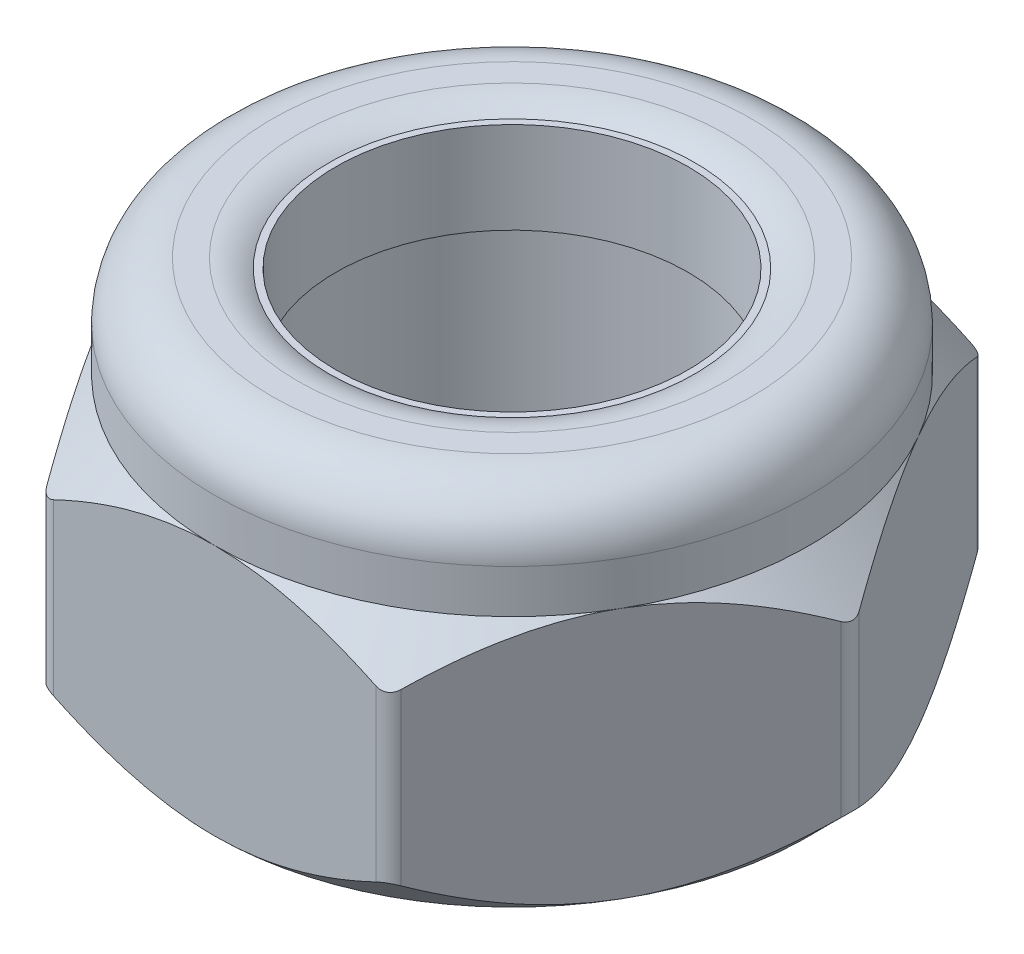
SolidWorks part; units mm, degrees
material "铸造碳钢"
ref_plane "Front" through (0, 0, 0) normal (0, 0, 1) x (1, 0, 0)
ref_plane "Top" through (0, 0, 0) normal (0, 1, 0) x (1, 0, 0)
ref_plane "Right" through (0, 0, 0) normal (1, 0, 0) x (0, 0, -1)
other "配置表"
sketch "草图1" plane through (0, 0, 0) normal (0, 1, 0) x (1, 0, 0)
  line L1 (7.5056, 0) -> (3.7528, 6.5)
  line L2 (3.7528, 6.5) -> (-3.7528, 6.5)
  line L3 (-3.7528, 6.5) -> (-7.5056, 0)
  line L4 (-7.5056, 0) -> (-3.7528, -6.5)
  line L5 (-3.7528, -6.5) -> (3.7528, -6.5)
  line L6 (3.7528, -6.5) -> (7.5056, 0)
  circle A0 centre (0, 0) radius 6.5 construction
  dimension "六角对边长" = 13
extrude "凸台-拉伸1" add sketch "草图1" along normal mid plane 5.5
sketch "草图3" plane through (0, 2.75, 0) normal (0, 1, 0) x (1, 0, 0)
  circle A0 centre (0, 0) radius 6.5
  dimension "圆形外直径" = 13
extrude "凸台-拉伸2" add sketch "草图3" along normal blind 2.2
sketch "草图4" plane through (0, 4.95, 0) normal (0, 1, 0) x (1, 0, 0)
  circle A0 centre (0, 0) radius 4
  dimension "螺母内径" = 8
extrude "切除-拉伸1" cut sketch "草图4" against normal through all
sketch "草图5" plane through (0, 4.95, 0) normal (0, 1, 0) x (1, 0, 0)
  circle A0 centre (0, 0) radius 4
  circle A1 centre (0, 0) radius 3.85
  dimension "橡胶内径" = 7.7
  dimension "橡皮圈外直径" = 8
extrude "凸台-拉伸3" add sketch "草图5" against normal up to surface (2.2 mm away) from offset 0.2 up to face at (-6.5449, 2.75, 0) offset against normal yes
fillet "圆角1" radius 1.25 2 edges at (0, 4.95, 4) (0, 4.95, 6.5)
sketch "草图6" plane through (0, 0, 0) normal (0, 0, 1) x (1, 0, 0)
  line L0 (0, -1000) -> (0, 49000) construction
  line L1 (-1000, 0) -> (49000, 0) construction
  line L2 (-7.5056, 2.75) -> (-7.5056, 1.7444)
  line L3 (-7.5056, 1.7444) -> (-6.5, 2.75)
  line L4 (-6.5, 2.75) -> (-7.5056, 2.75)
  line L5 (0, 2.75) -> (-5.6292, 2.75) construction
  line L6 (-7.5056, 2.75) -> (-7.5056, -2.75) construction
  line L7 (-6.5, -998.4247) -> (-6.5, 49001.5753) construction
  line L8 (-6.5, 3.7) -> (-6.5, 2.75) construction
  line L9 (-7.5056, -2.75) -> (-7.5056, -1.7444)
  line L10 (-7.5056, -1.7444) -> (-6.5, -2.75)
  line L11 (-6.5, -2.75) -> (-7.5056, -2.75)
  dimension "D1" = 45
revolve "切除-旋转1" cut sketch "草图6" angle 360 about L0
fillet "圆角3" radius 0.4 6 edges at (-7.5056, 0, 0) (-3.7528, 0, -6.5) (3.7528, 0, -6.5) (7.5056, 0, 0) (3.7528, 0, 6.5) (-3.7528, 0, 6.5)
move or copy body "实体-移动/复制1" [suppressed] bodies to move or copy 105
move or copy body "实体-移动/复制2" [suppressed] bodies to move or copy 105
